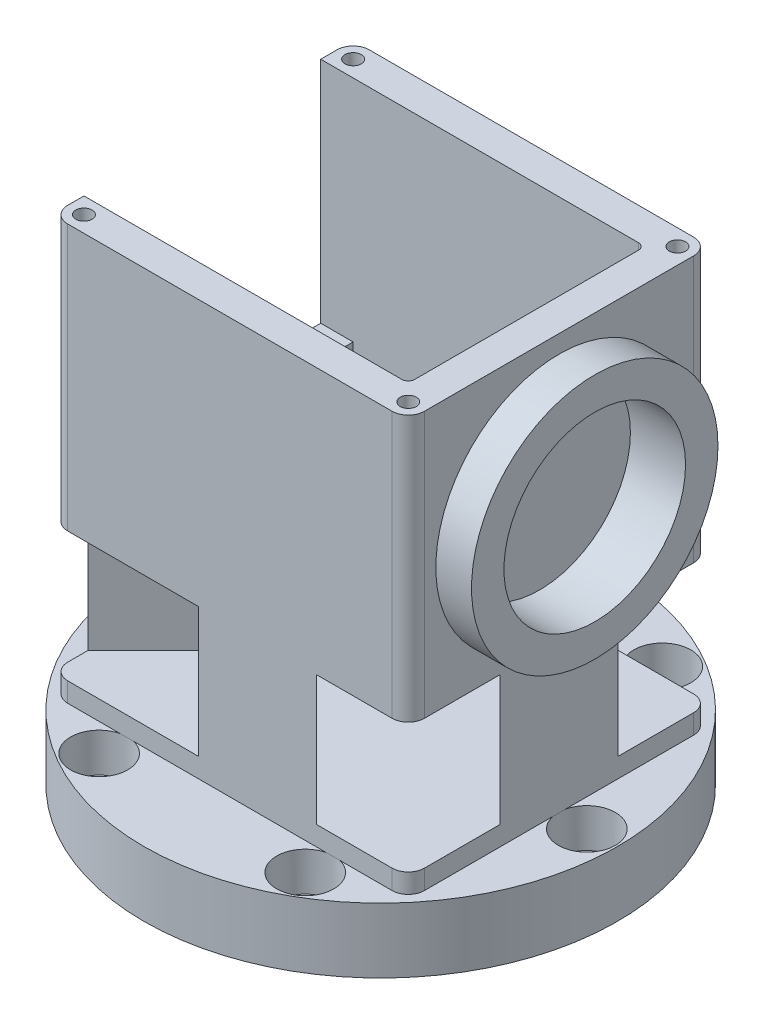
SolidWorks part; units mm, degrees
note: The reader was unsure of these and kept them because the rebuilt part matched: shared geometry of "Sketch1<2>", "Sketch7<2>".
ref_plane "Front Plane" through (0, 0, 0) normal (0, 0, 1) x (1, 0, 0)
ref_plane "Top Plane" through (0, 0, 0) normal (0, 1, 0) x (1, 0, 0)
ref_plane "Right Plane" through (0, 0, 0) normal (1, 0, 0) x (0, 0, -1)
sketch "Sketch1" plane through (0, 0, 0) normal (0, 1, 0) x (1, 0, 0)
  line L0 (0, 0) -> (0, 50000) construction
  line L1 (0, 0) -> (50000, 0) construction
  line L2 (-27.5, 23.25) -> (27.5, 23.25)
  line L3 (-22.5, 18.25) -> (22.5, 18.25)
  line L4 (-22.5, 18.25) -> (-22.5, -18.25)
  line L5 (-22.5, -18.25) -> (22.5, -18.25)
  line L6 (22.5, 18.25) -> (22.5, -18.25)
  line L7 (27.5, 23.25) -> (27.5, -23.25)
  line L8 (-27.5, -23.25) -> (27.5, -23.25)
  line L9 (-27.5, 23.25) -> (-27.5, -23.25)
  circle A0 centre (0, 0) radius 36.5
  circle A1 centre (0, 0) radius 31.78 construction
  circle A2 centre (-31.78, 0) radius 2.25
  circle A3 centre (-15.89, 27.5223) radius 2.25
  circle A4 centre (15.89, 27.5223) radius 2.25
  circle A5 centre (31.78, 0) radius 2.25
  circle A6 centre (15.89, -27.5223) radius 2.25
  circle A7 centre (-15.89, -27.5223) radius 2.25
  point P18 (0, 0)
  dimension "D1" = 73
  dimension "D2" = 63.56
  dimension "D3" = 4.5
  dimension "D5" = 45
  dimension "D6" = 36.5
  dimension "D7" = 5
  dimension "D4" = 6
extrude "Boss-Extrude1" add sketch "Sketch1" along normal blind 10 contours A0 A7 A6 A5 A4 A3 A2 L9 L2 L7 L8 | L6 L3 L4 L5
extrude "Boss-Extrude2" add sketch "Sketch1<2>" along normal blind 60 contours L2 L9 L8 L7 L3 L6 L5 L4
sketch "Sketch1<2>" plane through (0, 0, 0) normal (0, 1, 0) x (1, 0, 0) same geometry as "Sketch1"
fillet "Fillet2" radius 1 4 edges at (-22.5, 30, 18.25) (22.5, 30, 18.25) (22.5, 30, -18.25) (-22.5, 30, -18.25)
sketch "Sketch2" plane through (-22.5, 0, 0) normal (1, 0, 0) x (0, 0, -1)
  line L0 (18.25, 60) -> (18.25, 0) construction
  line L1 (-18.25, 0) -> (-18.25, 60) construction
  line L2 (18.25, 60) -> (18.25, 10)
  line L3 (-18.25, 10) -> (-18.25, 60)
  line L4 (-18.25, 60) -> (18.25, 60)
  line L5 (-18.25, 10) -> (18.25, 10)
  dimension "D1" = 50
extrude "Cut-Extrude1" cut sketch "Sketch2" against normal up to next and the other way up to next
sketch "Sketch3" plane through (-27.5, 0, 0) normal (-1, 0, 0) x (0, 0, 1)
  line L0 (-23.25, 60) -> (-23.25, 10) construction
  line L1 (-23.25, 23.75) -> (23.25, 23.75)
  line L2 (-23.25, 23.75) -> (-23.25, 10)
  line L3 (-23.25, 10) -> (23.25, 10)
  line L4 (23.25, 23.75) -> (23.25, 10)
  line L5 (-17.25, 60) -> (17.25, 60) construction
  dimension "D1" = 36.25
extrude "Boss-Extrude3" add sketch "Sketch3" against normal up to vertex
fillet "Fillet5" radius 2.5 4 edges at (-27.5, 35, 23.25) (-27.5, 35, -23.25) (27.5, 35, -23.25) (27.5, 35, 23.25)
sketch "Sketch6" plane through (0, 10, 0) normal (0, 1, 0) x (1, 0, 0)
  circle A0 centre (-15.89, 27.5223) radius 4.4
  circle A1 centre (15.89, 27.5223) radius 4.4
  circle A2 centre (31.78, 0) radius 4.4
  circle A3 centre (15.89, -27.5223) radius 4.4
  circle A4 centre (-15.89, -27.5223) radius 4.4
  circle A5 centre (-31.78, 0) radius 4.4
  dimension "D1" = 8.8
extrude "Cut-Extrude4" cut sketch "Sketch6" against normal blind 6
sketch "Sketch7" plane through (27.5, 0, 0) normal (1, 0, 0) x (0, 0, -1)
  line L0 (20.75, 60) -> (-20.75, 60) construction
  circle A0 centre (0, 52.25) radius 14
  circle A1 centre (0, 52.25) radius 19
  dimension "D2" = 28
  dimension "D1" = 7.75
  dimension "D3" = 5
extrude "Boss-Extrude4" add sketch "Sketch7" along normal blind 5.5
extrude "Cut-Extrude5" cut sketch "Sketch7<2>" against normal blind 3 contours A0
sketch "Sketch7<2>" plane through (27.5, 0, 0) normal (1, 0, 0) x (0, 0, -1) same geometry as "Sketch7"
sketch "Sketch8" plane through (0, 60, 0) normal (0, 1, 0) x (1, 0, 0)
  circle A0 centre (-25, 20.75) radius 1.25
  circle A1 centre (25, 20.75) radius 1.25
  circle A2 centre (25, -20.75) radius 1.25
  circle A3 centre (-25, -20.75) radius 1.25
  dimension "D1" = 2.5
extrude "Cut-Extrude6" cut sketch "Sketch8" against normal blind 11
sketch "Sketch9" plane through (0, 60, 0) normal (0, 1, 0) x (1, 0, 0)
  line L8 (21.5, -18.25) -> (-27.5, -18.25)
  line L9 (-27.5, -18.25) -> (-27.5, -20.75)
  line L10 (-25, -23.25) -> (25, -23.25)
  line L11 (27.5, -20.75) -> (27.5, -17.3476)
  line L12 (25, 23.25) -> (-25, 23.25)
  line L13 (21.5, -18.25) -> (-27.5, -18.25)
  line L14 (-27.5, 20.75) -> (-27.5, 18.25)
  line L15 (-27.5, 20.75) -> (-27.5, 18.25)
  line L17 (-27.5, -18.25) -> (-27.5, -20.75)
  line L18 (-25, -23.25) -> (25, -23.25)
  line L19 (27.5, -20.75) -> (27.5, -17.3476)
  line L20 (25, 23.25) -> (-25, 23.25)
  line L24 (-27.5, 18.25) -> (21.5, 18.25)
  line L25 (-27.5, 18.25) -> (21.5, 18.25)
  line L26 (22.5, 17.25) -> (22.5, -17.25)
  line L27 (22.5, 17.25) -> (22.5, -17.25)
  line L34 (27.5, -11.6592) -> (24.5, -11.6592)
  line L35 (27.5, -11.6592) -> (24.5, -11.6592)
  line L36 (24.5, -11.6592) -> (24.5, 11.6592)
  line L37 (24.5, -11.6592) -> (24.5, 11.6592)
  line L38 (24.5, 11.6592) -> (27.5, 11.6592)
  line L39 (24.5, 11.6592) -> (27.5, 11.6592)
  line L40 (27.5, 11.6592) -> (27.5, 17.3476)
  line L41 (27.5, 11.6592) -> (27.5, 17.3476)
  line L42 (27.5, 17.3476) -> (27.5, 20.75)
  line L43 (27.5, 17.3476) -> (27.5, 20.75)
  line L44 (27.5, -17.3476) -> (27.5, -11.6592)
  line L45 (27.5, -17.3476) -> (27.5, -11.6592)
  circle A0 centre (-25, 20.75) radius 1.25 construction
  circle A1 centre (25, 20.75) radius 1.25 construction
  circle A2 centre (25, -20.75) radius 1.25 construction
  circle A3 centre (-25, -20.75) radius 1.25 construction
  circle A7 centre (-25, -20.75) radius 1.25
  arc A9 (-27.5, -20.75) -> (-25, -23.25) centre (-25, -20.75) ccw
  arc A10 (25, -23.25) -> (27.5, -20.75) centre (25, -20.75) ccw
  arc A11 (27.5, 20.75) -> (25, 23.25) centre (25, 20.75) ccw
  arc A12 (-25, 23.25) -> (-27.5, 20.75) centre (-25, 20.75) ccw
  arc A15 (22.5, 17.25) -> (21.5, 18.25) centre (21.5, 17.25) ccw
  arc A17 (-27.5, -20.75) -> (-25, -23.25) centre (-25, -20.75) ccw
  arc A18 (25, -23.25) -> (27.5, -20.75) centre (25, -20.75) ccw
  arc A19 (27.5, 20.75) -> (25, 23.25) centre (25, 20.75) ccw
  arc A20 (-25, 23.25) -> (-27.5, 20.75) centre (-25, 20.75) ccw
  circle A24 centre (25, -20.75) radius 1.25
  circle A25 centre (25, 20.75) radius 1.25
  circle A26 centre (-25, 20.75) radius 1.25
  arc A27 (22.5, 17.25) -> (21.5, 18.25) centre (21.5, 17.25) ccw
  arc A28 (21.5, -18.25) -> (22.5, -17.25) centre (21.5, -17.25) ccw
  arc A29 (21.5, -18.25) -> (22.5, -17.25) centre (21.5, -17.25) ccw
  dimension "D1" = 0
extrude "Cut-Extrude7" cut sketch "Sketch9" against normal blind 1
sketch "Sketch11" plane through (0, 10, 0) normal (0, 1, 0) x (1, 0, 0)
  line L4 (22.5, -18.25) -> (22.5, 18.25)
  line L5 (22.5, 18.25) -> (-22.5, 18.25)
  line L6 (-22.5, 18.25) -> (-22.5, -18.25)
  line L7 (-22.5, -18.25) -> (22.5, -18.25)
  line L8 (22.5, -18.25) -> (22.5, 18.25)
  line L9 (22.5, 18.25) -> (-22.5, 18.25)
  line L10 (-22.5, 18.25) -> (-22.5, -18.25)
  line L11 (-22.5, -18.25) -> (22.5, -18.25)
  dimension "D1" = 0
extrude "Boss-Extrude5" add sketch "Sketch11" along normal blind 15
sketch "Sketch12" plane through (0, 23.75, 0) normal (0, 1, 0) x (1, 0, 0)
  line L4 (-22.5, 18.25) -> (-27.5, 18.25)
  line L5 (-27.5, 18.25) -> (-27.5, -18.25)
  line L6 (-27.5, -18.25) -> (-22.5, -18.25)
  line L7 (-22.5, -18.25) -> (-22.5, 18.25)
  line L8 (-22.5, 18.25) -> (-27.5, 18.25)
  line L9 (-27.5, 18.25) -> (-27.5, -18.25)
  line L10 (-27.5, -18.25) -> (-22.5, -18.25)
  line L11 (-22.5, -18.25) -> (-22.5, 18.25)
  dimension "D1" = 0
extrude "Boss-Extrude6" add sketch "Sketch12" along normal blind 15
sketch "Sketch13" plane through (0, 59, 0) normal (0, 1, 0) x (1, 0, 0)
  line L0 (27.5, 12.2653) -> (27.5, -12.2653)
  line L8 (-25, -23.25) -> (25, -23.25)
  line L9 (27.5, -20.75) -> (27.5, -17.7606)
  line L10 (25, 23.25) -> (-25, 23.25)
  line L11 (-27.5, 20.75) -> (-27.5, 18.25)
  line L12 (-27.5, 18.25) -> (21.5, 18.25)
  line L13 (22.5, 17.25) -> (22.5, -17.25)
  line L14 (21.5, -18.25) -> (-27.5, -18.25)
  line L15 (-27.5, -18.25) -> (-27.5, -20.75)
  line L16 (-25, -23.25) -> (25, -23.25)
  line L17 (27.5, -20.75) -> (27.5, -17.7606)
  line L18 (25, 23.25) -> (-25, 23.25)
  line L19 (-27.5, 20.75) -> (-27.5, 18.25)
  line L20 (-27.5, 18.25) -> (21.5, 18.25)
  line L21 (22.5, 17.25) -> (22.5, -17.25)
  line L22 (21.5, -18.25) -> (-27.5, -18.25)
  line L23 (-27.5, -18.25) -> (-27.5, -20.75)
  line L30 (27.5, 12.2653) -> (27.5, 17.7606)
  line L31 (27.5, 12.2653) -> (27.5, 17.7606)
  line L32 (27.5, 17.7606) -> (27.5, 20.75)
  line L33 (27.5, 17.7606) -> (27.5, 20.75)
  line L34 (27.5, -17.7606) -> (27.5, -12.2653)
  line L35 (27.5, -17.7606) -> (27.5, -12.2653)
  line L36 (27.5, -12.2653) -> (24.5, -12.2653)
  line L38 (24.5, -12.2653) -> (24.5, 12.2653)
  line L40 (24.5, 12.2653) -> (27.5, 12.2653)
  circle A0 centre (-25, -20.75) radius 1.25 construction
  circle A1 centre (25, -20.75) radius 1.25 construction
  circle A2 centre (25, 20.75) radius 1.25 construction
  circle A3 centre (-25, 20.75) radius 1.25 construction
  circle A4 centre (-25, -20.75) radius 1.25
  circle A5 centre (25, -20.75) radius 1.25
  arc A6 (-27.5, -20.75) -> (-25, -23.25) centre (-25, -20.75) ccw
  arc A7 (25, -23.25) -> (27.5, -20.75) centre (25, -20.75) ccw
  arc A8 (27.5, 20.75) -> (25, 23.25) centre (25, 20.75) ccw
  arc A9 (-25, 23.25) -> (-27.5, 20.75) centre (-25, 20.75) ccw
  arc A10 (22.5, 17.25) -> (21.5, 18.25) centre (21.5, 17.25) ccw
  arc A11 (21.5, -18.25) -> (22.5, -17.25) centre (21.5, -17.25) ccw
  arc A12 (-27.5, -20.75) -> (-25, -23.25) centre (-25, -20.75) ccw
  arc A13 (25, -23.25) -> (27.5, -20.75) centre (25, -20.75) ccw
  arc A14 (27.5, 20.75) -> (25, 23.25) centre (25, 20.75) ccw
  arc A15 (-25, 23.25) -> (-27.5, 20.75) centre (-25, 20.75) ccw
  arc A16 (22.5, 17.25) -> (21.5, 18.25) centre (21.5, 17.25) ccw
  arc A17 (21.5, -18.25) -> (22.5, -17.25) centre (21.5, -17.25) ccw
  circle A18 centre (25, 20.75) radius 1.25
  circle A19 centre (-25, 20.75) radius 1.25
  dimension "D1" = 0
extrude "Boss-Extrude7" add sketch "Sketch13" along normal blind 15
sketch "Sketch14" plane through (27.5, 0, 0) normal (1, 0, 0) x (0, 0, -1)
  line L1 (-12.2653, 59) -> (12.2653, 59)
  line L2 (-12.2653, 59) -> (12.2653, 59)
  arc A1 (12.2653, 59) -> (-12.2653, 59) centre (0, 52.25) ccw
  arc A2 (12.2653, 59) -> (-12.2653, 59) centre (0, 52.25) ccw
  dimension "D1" = 0
extrude "Cut-Extrude8" cut sketch "Sketch14" against normal up to surface (3 mm away) up to face at (24.5, 48.625, 0)
ref_plane "Plane1" through (26.7678, 74, -22.5178) normal (0.7071, 0, -0.7071) x (-0.7071, 0, -0.7071)
sketch "Sketch15" plane through (26.7678, 74, -22.5178) normal (0.7071, 0, -0.7071) x (-0.7071, 0, -0.7071)
  line L0 (0, 0) -> (0, 50000) construction
  line L1 (-10, -41) -> (10, -41)
  line L2 (-10, -41) -> (-10, -61)
  line L3 (-10, -61) -> (10, -61)
  line L4 (10, -41) -> (10, -61)
  line L5 (1.7678, 0) -> (-1.7678, 0) construction
  line L6 (39.5052, -64) -> (-33.4948, -64) construction
  point P8 (0, 0)
  dimension "D1" = 20
  dimension "D2" = 20
  dimension "D3" = 3
extrude "Cut-Extrude9" cut sketch "Sketch15" against normal through all
mirror "Mirror1" about plane through (0, 0, 0) normal (0, 0, 1) of "Cut-Extrude9"
